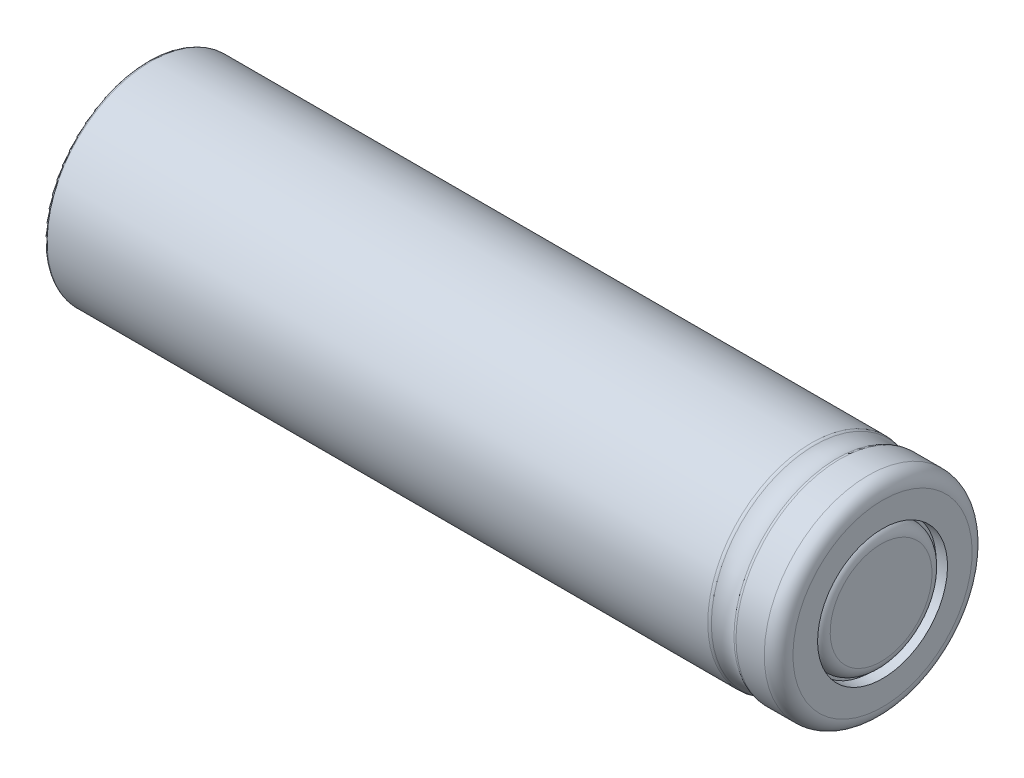
SolidWorks part; units mm, degrees
ref_plane "Front" through (0, 0, 0) normal (0, 0, 1) x (1, 0, 0)
ref_plane "Top" through (0, 0, 0) normal (0, 1, 0) x (1, 0, 0)
ref_plane "Right" through (0, 0, 0) normal (1, 0, 0) x (0, 0, -1)
sketch "Sketch1" plane through (0, 0, 0) normal (0, 0, 1) x (1, 0, 0)
  line L0 (0, 0) -> (0, 8.946)
  line L1 (0.254, 9.2) -> (63.73, 9.2)
  line L2 (65, 7.93) -> (65, 0)
  line L3 (65, 0) -> (0, 0)
  arc A0 (0.254, 9.2) -> (0, 8.946) centre (0.254, 8.946) ccw
  arc A1 (65, 7.93) -> (63.73, 9.2) centre (63.73, 7.93) ccw
  dimension "D1" = 0.254
  dimension "D4" = 1.27
  dimension "D2" = 65
  dimension "D3" = 9.2
revolve "base" add sketch "Sketch1" angle 360 about L3
sketch "Sketch2" plane through (0, 0, 0) normal (0, 0, 1) x (1, 0, 0)
  line L0 (63.73, 9.2) -> (61.23, 9.2)
  line L2 (0, 0) -> (64.5761, 0) construction
  line L3 (61.23, 9.2) -> (58.73, 9.2)
  line L4 (58.73, 9.2) -> (0, 9.2)
  arc A0 (60.98, 9.133) -> (58.98, 9.133) centre (59.98, 10.8651) cw
  arc A1 (58.98, 9.133) -> (58.73, 9.2) centre (58.73, 8.7) ccw
  arc A2 (61.23, 9.2) -> (60.98, 9.133) centre (61.23, 8.7) ccw
  point P0 (63.73, 9.2)
  dimension "D1" = 0.5
  dimension "D3" = 2
  dimension "D2" = 2.5
  dimension "D4" = 2.5
revolve "+ notch" cut sketch "Sketch2" angle 360 about L2 region at (59.98, 9.0658, 0)
sketch "Sketch3" plane through (65, 0, 0) normal (1, 0, 0) x (0, 0, -1)
  circle A0 centre (0, 0) radius 5.75
  dimension "D1" = 11.5
extrude "Extrude1" cut sketch "Sketch3" against normal blind 1.016
sketch "Sketch4" plane through (63.984, 0, 0) normal (1, 0, 0) x (0, 0, -1)
  circle A0 centre (0, 0) radius 5.5
  dimension "D1" = 11
extrude "Extrude3" add sketch "Sketch4" along normal offset from surface 0.127 up to face at (65, 5.75, 0)
sketch "Sketch5" plane through (0, 0, 0) normal (-1, 0, 0) x (0, 0, 1)
  circle A0 centre (0, 0) radius 7.5
  dimension "D1" = 15
extrude "Extrude4" cut sketch "Sketch5" against normal blind 0.0254
fillet "Fillet1" radius 1 1 edges at (64.873, 5.5, 0)
